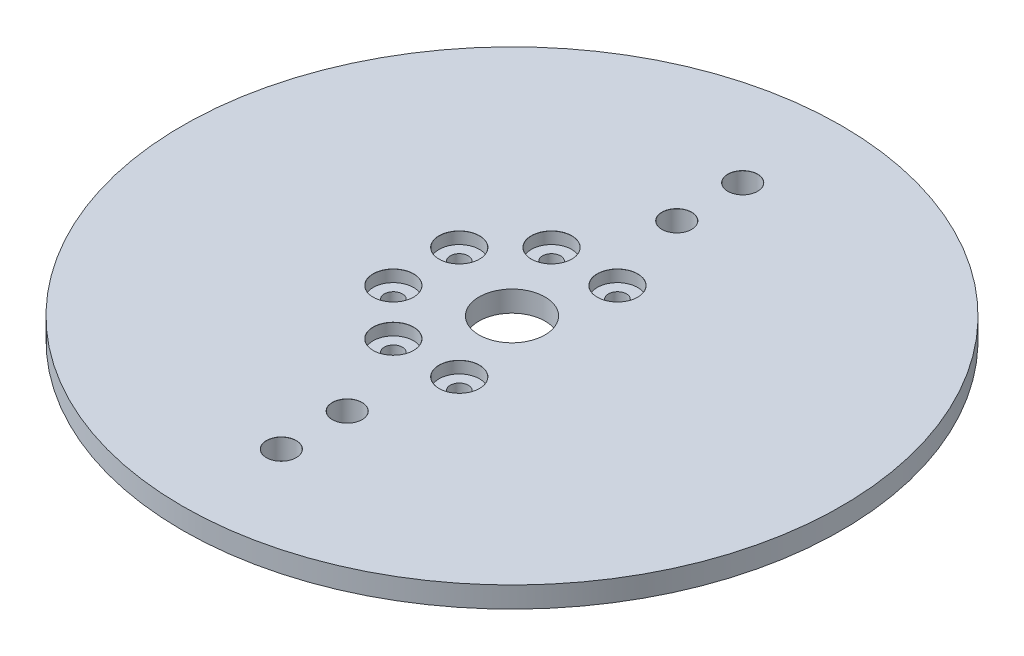
SolidWorks part; units mm, degrees
material "1060 Alloy"
ref_plane "Front Plane" through (0, 0, 0) normal (0, 0, 1) x (1, 0, 0)
ref_plane "Top Plane" through (0, 0, 0) normal (0, 1, 0) x (1, 0, 0)
ref_plane "Right Plane" through (0, 0, 0) normal (1, 0, 0) x (0, 0, -1)
sketch "Sketch1" plane through (0, 0, 0) normal (0, 1, 0) x (1, 0, 0)
  circle A0 centre (0, 0) radius 100
  dimension "D1" = 200
extrude "Boss-Extrude1" add sketch "Sketch1" along normal blind 6.35
sketch "Sketch2" plane through (0, 6.35, 0) normal (0, 1, 0) x (1, 0, 0)
  circle A0 centre (0, 0) radius 10
  dimension "D1" = 20
extrude "Cut-Extrude1" cut sketch "Sketch2" against normal through all
sketch "Sketch3" plane through (0, 6.35, 0) normal (0, 1, 0) x (1, 0, 0)
  line L0 (0, -70) -> (0, 70) construction
  point P3 (0, 0)
  point P4 (0, -50)
  point P6 (0, 50)
  dimension "D1" = 140
  dimension "D2" = 20
  dimension "D3" = 20
hole_wizard "M8 Clearance Hole1" positions "Sketch4" profile "Sketch5" hole size "M8" standard "ANSI Metric" end condition through all
sketch "Sketch4" plane through (0, 6.35, 0) normal (0, 1, 0) x (1, 0, 0)
  point P0 (0, 70)
  point P3 (0, 50)
  point P6 (0, -50)
  point P9 (0, -70)
sketch "Sketch5" plane through (0, 6.35, -70) normal (1, 0, 0) x (0, 0, 1)
  line L0 (0, 0) -> (0, 6.35)
  line L1 (0, 6.35) -> (4.5, 6.35)
  line L2 (4.5, 6.35) -> (4.5, 0.025)
  line L3 (4.5, 0.025) -> (4.525, 0)
  line L5 (4.525, 0) -> (0, 0)
  line L6 (-4.5, 0.025) -> (-4.525, 0) construction
  line L11 (0, -6.35) -> (0, 107.95) construction
  dimension "Thru Hole Dia." = 9
  dimension "Thru Hole Depth" = 6.35
  dimension "Near C'Sink Dia." = 9.05
  dimension "Near C'Sink Angle" = 90
sketch "Sketch6" plane through (0, 6.35, 0) normal (0, 1, 0) x (1, 0, 0)
  line L0 (-3.4925, 0) -> (3.4925, 0) construction
  point P0 (-26, 10)
  point P1 (-12, 24)
  point P2 (8, 24)
  point P3 (8, 24)
  point P4 (10.9552, 28.084)
  point P5 (-24.8929, 26.0542)
  point P7 (0, 0)
  point P9 (-40.3375, -100.2942)
  point P12 (8, -24)
  point P13 (-12, -24)
  point P14 (-26, -10)
  dimension "D1" = 8
  dimension "D2" = 24
  dimension "D3" = 26
  dimension "D4" = 20
  dimension "D5" = 10
hole_wizard "CBORE for M5 Hex Head Bolt1" positions "Sketch7" profile "Sketch8" counterbore size "M5" standard "ANSI Metric" end condition through all
sketch "Sketch7" plane through (0, 6.35, 0) normal (0, 1, 0) x (1, 0, 0)
  point P0 (-26, 10)
  point P3 (-12, 24)
  point P6 (8, 24)
  point P9 (-26, -10)
  point P12 (-12, -24)
  point P15 (8, -24)
sketch "Sketch8" plane through (-26, 6.35, -10) normal (1, 0, 0) x (0, 0, 1)
  line L0 (0, 0) -> (0, 6.35)
  line L1 (0, 6.35) -> (2.75, 6.35)
  line L3 (2.75, 6.35) -> (2.75, 3.58)
  line L4 (6.12, 3.58) -> (2.75, 3.58)
  line L5 (6.12, 3.58) -> (6.12, 0.025)
  line L6 (6.12, 0.025) -> (6.145, 0)
  line L7 (6.145, 0) -> (0, 0)
  line L8 (-6.12, 0.025) -> (-6.145, 0) construction
  line L11 (0, -6.35) -> (0, 107.95) construction
  dimension "Thru Hole Dia." = 5.5
  dimension "Thru Hole Depth" = 6.35
  dimension "C'Bore Dia." = 12.24
  dimension "C'Bore Depth" = 3.58
  dimension "Near C'Sink Dia." = 12.29
  dimension "Near C'Sink Angle" = 90
